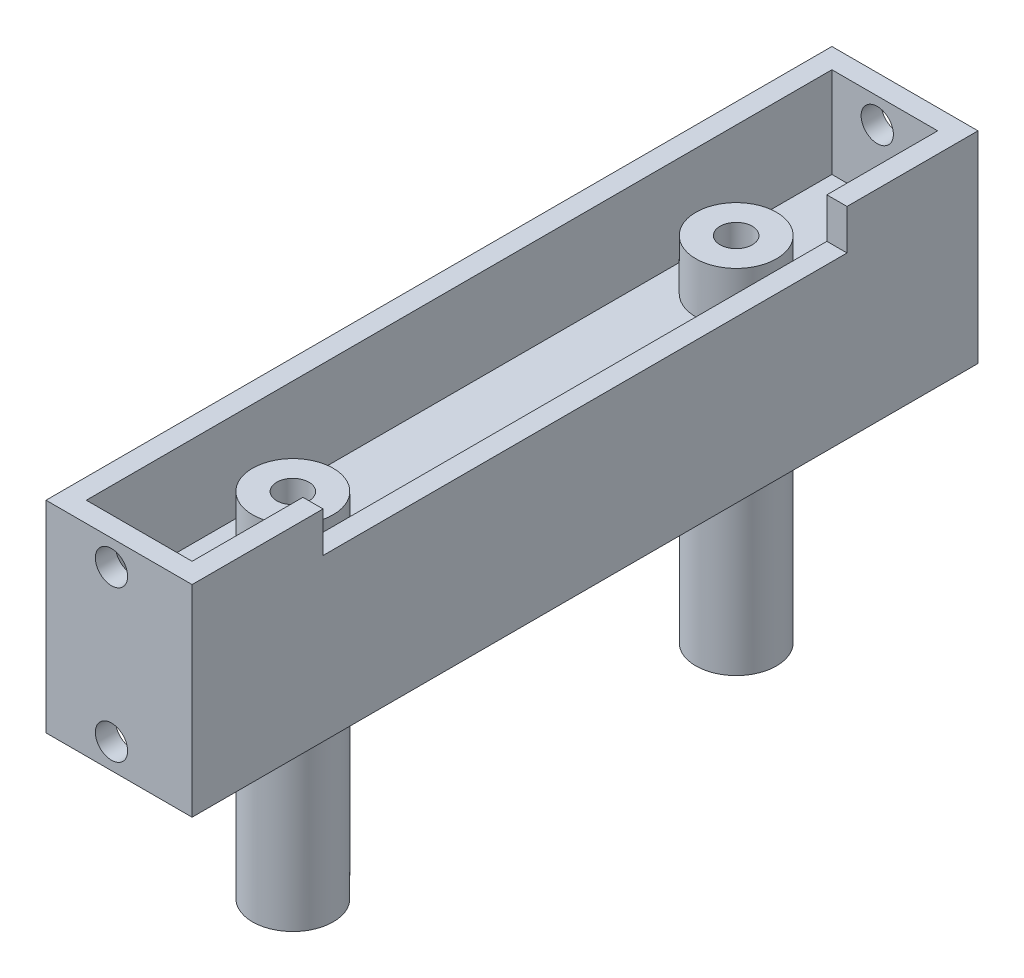
SolidWorks part; units mm, degrees
material "PET"
ref_plane "前视基准面" through (0, 0, 0) normal (0, 0, 1) x (1, 0, 0)
ref_plane "上视基准面" through (0, 0, 0) normal (0, 1, 0) x (1, 0, 0)
ref_plane "右视基准面" through (0, 0, 0) normal (1, 0, 0) x (0, 0, -1)
other "Configuration Table"
sketch "草图1" plane through (0, 0, 0) normal (0, 1, 0) x (1, 0, 0)
  line L1 (-30, -39) -> (30, -39)
  line L2 (-30, -39) -> (-30, 39)
  line L3 (-30, 39) -> (30, 39)
  line L4 (30, -39) -> (30, 39)
  line L5 (-30, -39) -> (30, 39) construction
  line L6 (-30, 39) -> (30, -39) construction
  point P0 (0, 0)
  dimension "D1" = 60
  dimension "D2" = 78
extrude "凸台-拉伸1" add sketch "草图1" along normal blind 2
sketch "草图2" plane through (0, 2, 0) normal (0, 1, 0) x (1, 0, 0)
  line L0 (-30, 0) -> (30, 0) construction
  line L1 (-30, 39) -> (-30, -39) construction
  line L2 (30, -39) -> (30, 39) construction
  line L3 (-24.5, 0) -> (-24.5, 22) construction
  circle A0 centre (-24.5, 22) radius 1.6
  circle A1 centre (19.5, 22) radius 1.6
  circle A2 centre (19.5, -22) radius 1.6
  circle A3 centre (-24.5, -22) radius 1.6
  dimension "D3" = 3.2
  dimension "D4" = 44
  dimension "D5" = 22
  dimension "D6" = 3.2
  dimension "D1" = 22
  dimension "D2" = 5.5
extrude "切除-拉伸1" cut sketch "草图2" against normal blind 12
sketch "草图3" plane through (0, 0, 39) normal (0, 0, 1) x (1, 0, 0)
  line L0 (-30, 2) -> (30, 0) construction
  line L1 (30, 2) -> (-30, 0) construction
  line L3 (-30, -9) -> (30, -9)
  line L4 (-30, -9) -> (-30, 11)
  line L5 (-30, 11) -> (30, 11)
  line L6 (30, -9) -> (30, 11)
  line L7 (-30, -9) -> (30, 11) construction
  line L8 (-30, 11) -> (30, -9) construction
  point P8 (0, 1)
  dimension "D1" = 20
extrude "凸台-拉伸2" add sketch "草图3" against normal blind 2
ref_plane "基准面1" through (0, 0, 0) normal (0, 0, 1) x (1, 0, 0)
mirror "镜向1" about plane through (0, 0, 0) normal (0, 0, 1) of "凸台-拉伸2"
sketch "草图4" plane through (0, 0, 39) normal (0, 0, 1) x (1, 0, 0)
  line L0 (-30, 1) -> (30, 1) construction
  line L1 (-30, 11) -> (-30, -9) construction
  line L2 (30, 11) -> (30, -9) construction
  line L3 (-25.5, 1) -> (-25.5, 8.5) construction
  line L4 (0, 11) -> (0, -9) construction
  line L5 (30, 11) -> (-30, 11) construction
  line L6 (-30, -9) -> (30, -9) construction
  circle A0 centre (-25.5, 8.5) radius 1.6
  circle A1 centre (-25.5, -6.5) radius 1.6
  circle A2 centre (25.5, -6.5) radius 1.6
  circle A3 centre (25.5, 8.5) radius 1.6
  dimension "D1" = 3.2
  dimension "D3" = 25.5
  dimension "D2" = 7.5
extrude "切除-拉伸2" cut sketch "草图4" against normal blind 126
sketch "草图5" plane through (0, 2, 0) normal (0, 1, 0) x (1, 0, 0)
  line L0 (0, 37) -> (0, -37) construction
  line L1 (30, 37) -> (-30, 37) construction
  line L2 (30, -37) -> (-30, -37) construction
  line L6 (-5.775, 0) -> (5.775, 0) construction
  circle A1 centre (-22.5, 32) radius 1.9469
  circle A2 centre (-7.5, 32) radius 1.9469
  circle A3 centre (7.5, 32) radius 1.9469
  circle A4 centre (22.5, 32) radius 1.9469
  circle A5 centre (22.5, -32) radius 1.9469
  circle A6 centre (7.5, -32) radius 1.9469
  circle A7 centre (-7.5, -32) radius 1.9469
  circle A8 centre (-22.5, -32) radius 1.9469
  dimension "D1" = 32
  dimension "D2" = 22.5
  dimension "D3" = 4
sketch "草图6" plane through (0, 2, 0) normal (0, 1, 0) x (1, 0, 0)
  circle A0 centre (-24.5, 22) radius 4
  circle A1 centre (19.5, 22) radius 4
  circle A2 centre (-24.5, -22) radius 4
  circle A3 centre (19.5, -22) radius 4
  circle A4 centre (-24.5, 22) radius 1.6
  circle A5 centre (19.5, 22) radius 1.6
  circle A6 centre (-24.5, -22) radius 1.6
  circle A8 centre (19.5, -22) radius 1.6
  dimension "D1" = 8
  dimension "D2" = 8
  dimension "D3" = 8
  dimension "D4" = 8
  dimension "D5" = 3.2
  dimension "D6" = 3.2
  dimension "D7" = 3.2
  dimension "D8" = 3.2
extrude "凸台-拉伸3" add sketch "草图6" against normal blind 30 and the other way blind 5
fillet "圆角1" radius 2 2 edges at (0, 0, 37) (0, 0, -37)
sketch "草图7" plane through (0, 0, -39) normal (0, 0, -1) x (-1, 0, 0)
  line L0 (0, 11) -> (0, 9) construction
  line L1 (-30, 11) -> (30, 11) construction
  circle A0 centre (0, 9) radius 1.5
  dimension "D2" = 3
  dimension "D1" = 2
extrude "切除-拉伸4" cut sketch "草图7" against normal blind 81
sketch "草图8" plane through (0, 0, -39) normal (0, 0, -1) x (-1, 0, 0)
  line L0 (30, -9) -> (-30, -9) construction
  circle A0 centre (0, -9) radius 2.5
  dimension "D1" = 5
extrude "切除-拉伸5" cut sketch "草图8" against normal blind 113
sketch "草图9" plane through (0, 2, 0) normal (0, 1, 0) x (1, 0, 0)
  circle A0 centre (-24.5, -22) radius 3
  circle A1 centre (19.5, -22) radius 3
  circle A2 centre (-24.5, 22) radius 3
  circle A3 centre (19.5, 22) radius 3
  dimension "D1" = 6
  dimension "D2" = 6
  dimension "D3" = 6
  dimension "D4" = 6
sketch "草图10" plane through (0, 0, 0) normal (0, -1, 0) x (-1, 0, 0)
  line L0 (-11, 0) -> (11, 0) construction
  line L1 (33.2702, 23.1872) -> (-14.7787, 23.1872)
  line L2 (33.2702, 23.1872) -> (33.2702, -23.1872)
  line L3 (33.2702, -23.1872) -> (-14.7787, -23.1872)
  line L4 (-14.7787, 23.1872) -> (-14.7787, -23.1872)
  line L5 (33.2702, 23.1872) -> (-14.7787, -23.1872) construction
  line L6 (33.2702, -23.1872) -> (-14.7787, 23.1872) construction
  point P0 (9.2458, 0)
sketch "草图11" plane through (0, 2, 0) normal (0, 1, 0) x (1, 0, 0)
  line L0 (-24.5, 22) -> (19.5, -22) construction
  line L1 (19.5, 22) -> (-24.5, -22) construction
  line L3 (-18.5, -16) -> (13.5, -16)
  line L4 (-18.5, -16) -> (-18.5, 16)
  line L5 (-18.5, 16) -> (13.5, 16)
  line L6 (13.5, -16) -> (13.5, 16)
  line L7 (-18.5, -16) -> (13.5, 16) construction
  line L8 (-18.5, 16) -> (13.5, -16) construction
  point P8 (-2.5, 0)
  dimension "D1" = 32
extrude "切除-拉伸6" cut sketch "草图11" against normal blind 10
fillet "圆角2" radius 5 4 edges at (13.5, 1, 16) (-18.5, 1, 16) (-18.5, 1, -16) (13.5, 1, -16)
sketch "草图12" plane through (0, 0, 0) normal (0, -1, 0) x (-1, 0, 0)
  line L0 (19.5, -39) -> (-30, -39)
  line L1 (30, -39) -> (2.5, -39) construction
  line L2 (-30, -39) -> (-30, 39)
  line L3 (-30, 39) -> (19.5, 39)
  line L4 (30, 39) -> (2.5, 39) construction
  line L5 (19.5, 39) -> (19.5, -39)
  circle A0 centre (24.5, -22) radius 4 construction
  dimension "D1" = 5
extrude "切除-拉伸7" cut sketch "草图12" against normal blind 40 and the other way blind 79 contours L5 L0 L2 L3
sketch "草图13" plane through (-30, 0, 0) normal (-1, 0, 0) x (0, 0, 1)
  line L1 (-39, 11) -> (39, 11)
  line L2 (-39, 11) -> (-39, -9)
  line L3 (-39, -9) -> (39, -9)
  line L4 (39, 11) -> (39, -9)
extrude "凸台-拉伸4" add sketch "草图13" along normal blind 2
sketch "草图14" plane through (-19.5, 0, 0) normal (1, 0, 0) x (0, 0, -1)
  line L1 (-39, 11) -> (39, 11)
  line L2 (-39, 11) -> (-39, -9)
  line L3 (-39, -9) -> (39, -9)
  line L4 (39, 11) -> (39, -9)
extrude "凸台-拉伸5" add sketch "草图14" along normal blind 2
sketch "草图15" plane through (0, 11, 0) normal (0, 1, 0) x (1, 0, 0)
  line L0 (-17.5, 39) -> (-17.5, -39) construction
  line L1 (-10.5, -26) -> (-24.5, -26)
  line L2 (-10.5, -26) -> (-10.5, 26)
  line L3 (-10.5, 26) -> (-24.5, 26)
  line L4 (-24.5, -26) -> (-24.5, 26)
  line L5 (-10.5, -26) -> (-24.5, 26) construction
  line L6 (-10.5, 26) -> (-24.5, -26) construction
  circle A0 centre (-24.5, 22) radius 4 construction
  circle A1 centre (-24.5, 22) radius 4 construction
  point P0 (-17.5, 0)
extrude "切除-拉伸8" cut sketch "草图15" against normal up to surface (4 mm away) up to face at (-24.5, 7, -18)
